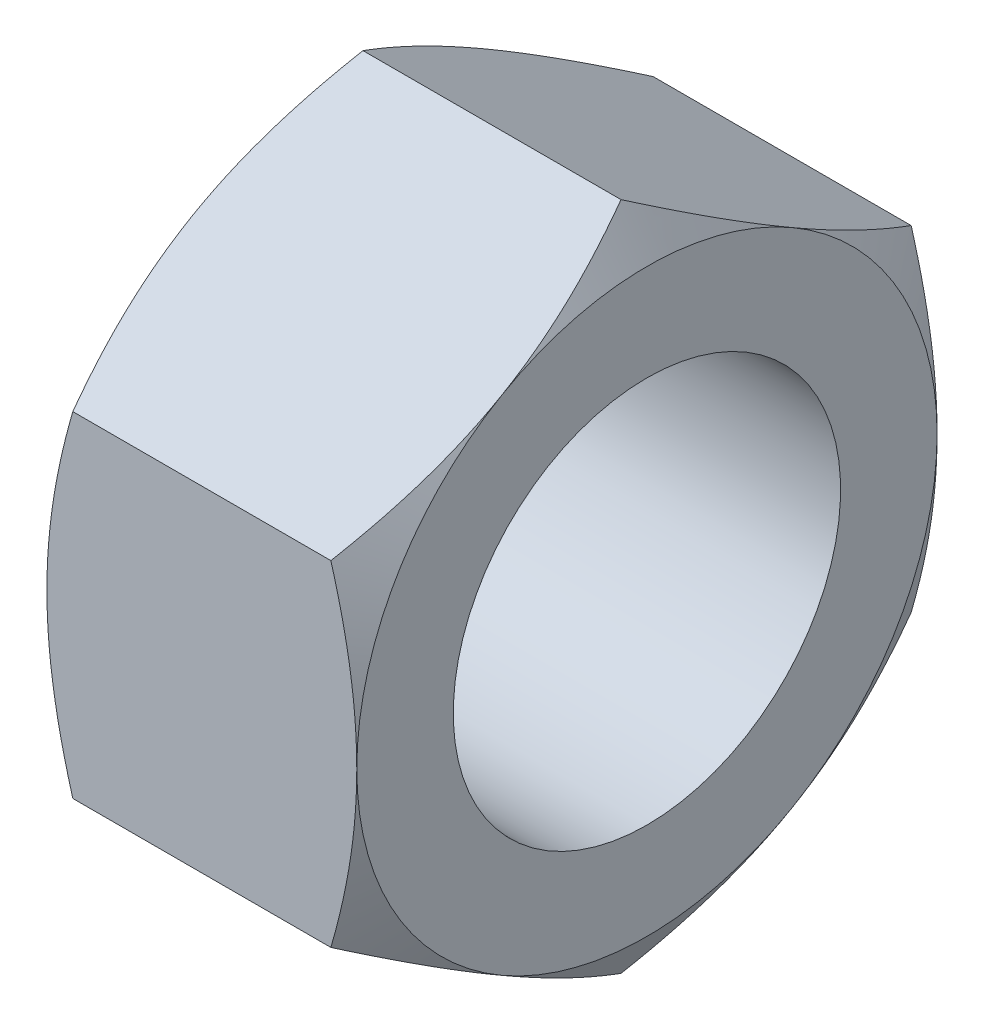
SolidWorks part; units mm, degrees
material "1.5714 (16NiCr4)"
ref_plane "Alzado" through (0, 0, 0) normal (0, 0, 1) x (1, 0, 0)
ref_plane "Planta" through (0, 0, 0) normal (0, 1, 0) x (1, 0, 0)
ref_plane "Vista lateral" through (0, 0, 0) normal (1, 0, 0) x (0, 0, -1)
sketch "Croquis1" plane through (0, 0, 0) normal (0, 0, 1) x (1, 0, 0)
  line L2 (0, 0) -> (0, 6.92)
  line L3 (0, 6.92) -> (6.4, 6.92)
  line L4 (6.4, 6.92) -> (6.4, 0)
  line L5 (6.4, 0) -> (0, 0)
  dimension "D3" = 6.92
  dimension "D4" = 6.4
revolve "Revolución1" add sketch "Croquis1" angle 360 about L5
sketch "Croquis2" plane through (6.4, 0, 0) normal (1, 0, 0) x (0, 0, -1)
  line L0 (0, 0) -> (0, 10.7677) construction
  line L1 (0, 6.92) -> (-5.9929, 3.46)
  line L2 (-5.9929, 3.46) -> (-5.9929, -3.46)
  line L3 (-5.9929, -3.46) -> (0, -6.92)
  line L4 (0, -6.92) -> (5.9929, -3.46)
  line L5 (5.9929, -3.46) -> (5.9929, 3.46)
  line L6 (5.9929, 3.46) -> (0, 6.92)
  circle A0 centre (0, 0) radius 5.9929 construction
  point P11 (0, 6.92)
  circle M7 centre (0, 0) radius 6.92
  dimension "D1" = 11.9858
extrude "Cortar-Extruir1" cut sketch "Croquis2" against normal blind 7 contours L2 M7 | L1 M7 | L6 M7 | L5 M7 | L4 M7 | L3 M7 region at (6.4, 5.5131, -3.183) region at (6.4, 5.5131, 3.183) region at (6.4, 0, 6.366) region at (6.4, 0, -6.366) region at (6.4, -5.5131, 3.183) region at (6.4, -5.5131, -3.183)
sketch "Croquis3" plane through (6.4, 0, 0) normal (1, 0, 0) x (0, 0, -1)
  circle A0 centre (0, 0) radius 5.9929
  dimension "D1" = 11.9858
extrude "Cortar-Extruir2" cut sketch "Croquis3" against normal blind 7 draft 60 flip side to cut
sketch "Croquis5" plane through (0, 0, 0) normal (-1, 0, 0) x (0, 0, 1)
  circle A0 centre (0, 0) radius 5.9929
  dimension "D1" = 11.9858
extrude "Cortar-Extruir3" cut sketch "Croquis5" against normal blind 1 draft 60 flip side to cut
sketch "Croquis6" plane through (6.4, 0, 0) normal (1, 0, 0) x (0, 0, -1)
  circle A0 centre (0, 0) radius 4
  dimension "D1" = 8
extrude "Cortar-Extruir4" cut sketch "Croquis6" against normal blind 7
